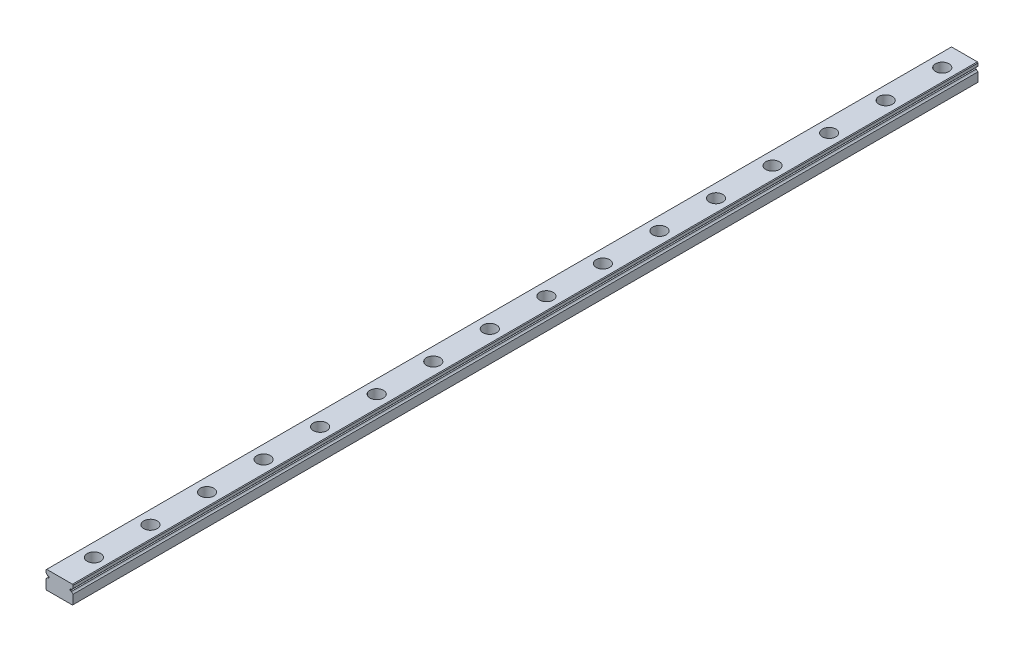
SolidWorks part; units mm, degrees
ref_plane "Спереди" through (0, 0, 0) normal (0, 0, 1) x (1, 0, 0)
ref_plane "Сверху" through (0, 0, 0) normal (0, 1, 0) x (1, 0, 0)
ref_plane "Справа" through (0, 0, 0) normal (1, 0, 0) x (0, 0, -1)
sketch "Эскиз1" plane through (0, 0, 0) normal (0, 0, 1) x (1, 0, 0)
  line L0 (-6, 3.7) -> (-5.7, 4)
  line L1 (-5.7, -4) -> (5.7, -4)
  line L2 (-6, -3.7) -> (-6, 0.3334)
  line L3 (-5.7, 4) -> (5.7, 4)
  line L4 (6, -3.7) -> (6, 0.3334)
  line L5 (-6, -4) -> (6, 4) construction
  line L6 (-6, 4) -> (6, -4) construction
  line L7 (-6, -3.7) -> (-5.7, -4)
  line L8 (5.7, -4) -> (6, -3.7)
  line L9 (5.7, 4) -> (6, 3.7)
  line L10 (-6, 2.4498) -> (-6, 3.7)
  line L11 (-5.2979, 1.7203) -> (-4.6875, 1.7203)
  line L12 (0, 5.4188) -> (0, -5.747) construction
  line L13 (-5.2922, 1.0823) -> (-4.6875, 1.0823)
  line L14 (-4.6875, 1.7203) -> (-4.6875, 1.0823)
  line L15 (4.6875, 1.7203) -> (4.6875, 1.0823)
  line L16 (5.2922, 1.0823) -> (4.6875, 1.0823)
  line L17 (5.2979, 1.7203) -> (4.6875, 1.7203)
  line L18 (6, 2.4498) -> (6, 3.7)
  arc A0 (-6, 0.3334) -> (-5.2922, 1.0823) centre (-6.3695, 1.3916) ccw
  arc A1 (-5.2979, 1.7203) -> (-6, 2.4498) centre (-6.3695, 1.3916) ccw
  arc A2 (5.2979, 1.7203) -> (6, 2.4498) centre (6.3695, 1.3916) cw
  arc A3 (6, 0.3334) -> (5.2922, 1.0823) centre (6.3695, 1.3916) cw
  point P0 (0, 0)
extrude "Бобышка-Вытянуть1" add sketch "Эскиз1" along normal blind 400
sketch "Эскиз2" plane through (0, 4, 0) normal (0, 1, 0) x (1, 0, 0)
  line L0 (0, 0) -> (0, -26.2396) construction
  line L1 (5.7, 0) -> (-5.7, 0) construction
  line L2 (-3.8306, -10) -> (4.207, -10) construction
  circle A0 centre (0.1882, -10) radius 3
  circle A1 centre (0.1882, -10) radius 1.75
  dimension "D1" = 10
extrude "Вырез-Вытянуть1" cut sketch "Эскиз2" against normal blind 4.5
extrude "Вырез-Вытянуть2" cut sketch "Эскиз2<2>" against normal through all contours A1 region at (0.1882, 4, 10)
sketch "Эскиз2<2>" plane through (0, 4, 0) normal (0, 1, 0) x (1, 0, 0) same geometry as "Эскиз2"
pattern_linear "Линейный массив1" count 16 spacing 25 along (0, 0, 1) of "Вырез-Вытянуть1", "Вырез-Вытянуть2"
